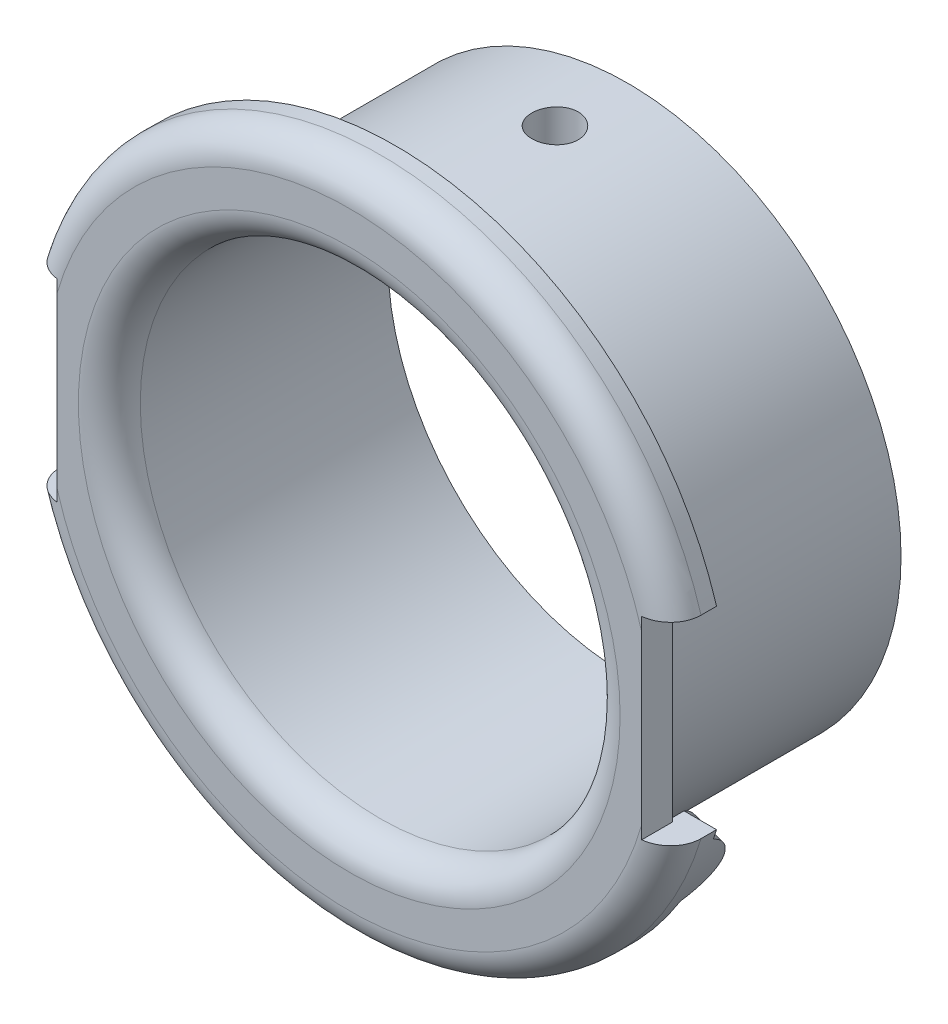
SolidWorks part; units mm, degrees
material "Custom Plastic"
ref_plane "X-Y Datum" through (0, 0, 0) normal (0, 0, 1) x (1, 0, 0)
ref_plane "X-Z Datum" through (0, 0, 0) normal (0, 1, 0) x (1, 0, 0)
ref_plane "Y-Z Datum" through (0, 0, 0) normal (1, 0, 0) x (0, 0, -1)
sketch "Sketch1" plane through (0, 0, 0) normal (0, 0, 1) x (1, 0, 0)
  circle A0 centre (0, 0) radius 17.65
  circle A1 centre (0, 0) radius 15.5
  dimension "D1" = 35.3
  dimension "D2" = 31
extrude "Boss-Extrude1" add sketch "Sketch1" along normal blind 18
sketch "Sketch2" plane through (0, 0, 18) normal (0, 0, 1) x (1, 0, 0)
  circle A0 centre (0, 0) radius 15.5
  circle A1 centre (0, 0) radius 21.65
  circle A2 centre (0, 0) radius 15.5 construction
  dimension "D1" = 43.3
extrude "Boss-Extrude2" add sketch "Sketch2" against normal blind 2
sketch "Sketch3" plane through (0, 0, 18) normal (0, 0, 1) x (1, 0, 0)
  line L0 (0, 15.5) -> (0, -15.5) construction
  line L1 (18.88, -6.25) -> (23.88, -6.25)
  line L2 (18.88, -6.25) -> (18.88, 6.25)
  line L3 (18.88, 6.25) -> (23.88, 6.25)
  line L4 (23.88, -6.25) -> (23.88, 6.25)
  line L5 (-18.88, -6.25) -> (-23.88, -6.25)
  line L6 (-23.88, -6.25) -> (-23.88, 6.25)
  line L7 (-18.88, 6.25) -> (-23.88, 6.25)
  line L8 (-18.88, -6.25) -> (-18.88, 6.25)
  circle A0 centre (0, 0) radius 15.5 construction
  point P4 (18.88, 0)
  dimension "D1" = 18.88
  dimension "D2" = 12.5
  dimension "D3" = 5
extrude "Cut-Extrude1" cut sketch "Sketch3" against normal through all
sketch "Sketch4" plane through (0, 0, 16) normal (0, 0, -1) x (-1, 0, 0)
  line L0 (-20.7282, -6.25) -> (-18.6295, -6.25)
  line L1 (-18.88, -6.25) -> (-20.7282, -6.25) construction
  line L2 (-20.7282, 6.25) -> (-18.6295, 6.25)
  line L3 (20.7282, -6.25) -> (18.6295, -6.25)
  line L4 (20.7282, 6.25) -> (18.6295, 6.25)
  arc A0 (-20.7282, -6.25) -> (20.7282, -6.25) centre (0, 0) ccw
  arc A1 (-18.6295, -6.25) -> (18.6295, -6.25) centre (0, 0) ccw
  arc A2 (-20.7282, -6.25) -> (20.7282, -6.25) centre (0, 0) ccw construction
  arc A3 (20.7282, 6.25) -> (-20.7282, 6.25) centre (0, 0) ccw
  arc A4 (18.6295, 6.25) -> (-18.6295, 6.25) centre (0, 0) ccw
  dimension "D1" = 2
extrude "Boss-Extrude3" add sketch "Sketch4" along normal blind 1
sketch "Sketch5" plane through (0, 0, 15) normal (0, 0, -1) x (-1, 0, 0)
  line L0 (-18.6295, -6.25) -> (-20.5257, -6.8861)
  line L1 (-16.699, -10.357) -> (-18.3986, -11.4111)
  line L2 (0, 0) -> (0, 22.5433) construction
  line L3 (0, 0) -> (-18.6295, -6.25) construction
  line L4 (0, 0) -> (-27.8603, 0) construction
  line L5 (0, 0) -> (-16.699, -10.357) construction
  line L6 (0, 0) -> (0, -24.6533) construction
  arc A0 (-20.7282, -6.25) -> (20.7282, -6.25) centre (0, 0) ccw construction
  arc A1 (-18.3986, -11.4111) -> (-20.5257, -6.8861) centre (0, 0) cw
  arc A2 (-16.699, -10.357) -> (-18.6295, -6.25) centre (0, 0) cw
  arc A3 (-18.6295, -6.25) -> (18.6295, -6.25) centre (0, 0) ccw construction
  arc A4 (-16.7334, -5.6139) -> (-14.9993, -9.3028) centre (0, 0) ccw construction
  arc A5 (-17.6815, -5.9319) -> (-15.8491, -9.8299) centre (0, 0) ccw construction
  dimension "D3" = 13.262
  dimension "D4" = 58.192
  dimension "D1" = 5
  dimension "D2" = 4.3072
extrude "Boss-Extrude4" add sketch "Sketch5" along normal blind 1.5
sketch3d "3DSketch1"
  line L0 (0, 0, 0) -> (0, 0, 18)
pattern_circular "CirPattern1" count 2 over 360 about axis through (0, 0, 0) along (0, 0, 1) of "Boss-Extrude4"
fillet "Fillet1" radius 3 4 edges at (-17.5488, 10.8841, 13.5) (-19.5776, 6.5681, 13.5) (17.5488, -10.8841, 13.5) (19.5776, -6.5681, 13.5)
fillet "Fillet2" radius 2 3 edges at (0, 21.65, 18) (15.5, 0, 18) (0, -21.65, 18)
sketch "Sketch6" plane through (0, 0, 0) normal (0, 1, 0) x (1, 0, 0)
  line L0 (-18.88, -18) -> (18.88, -18) construction
  circle A0 centre (0, -4.71) radius 2.5
  circle A1 centre (0, -4.71) radius 1.5
  dimension "D2" = 5
  dimension "D3" = 3
  dimension "D1" = 13.29
extrude "Cut-Extrude2" cut sketch "Sketch6" along normal through all contours A1 region at (0, 0, 4.71)
